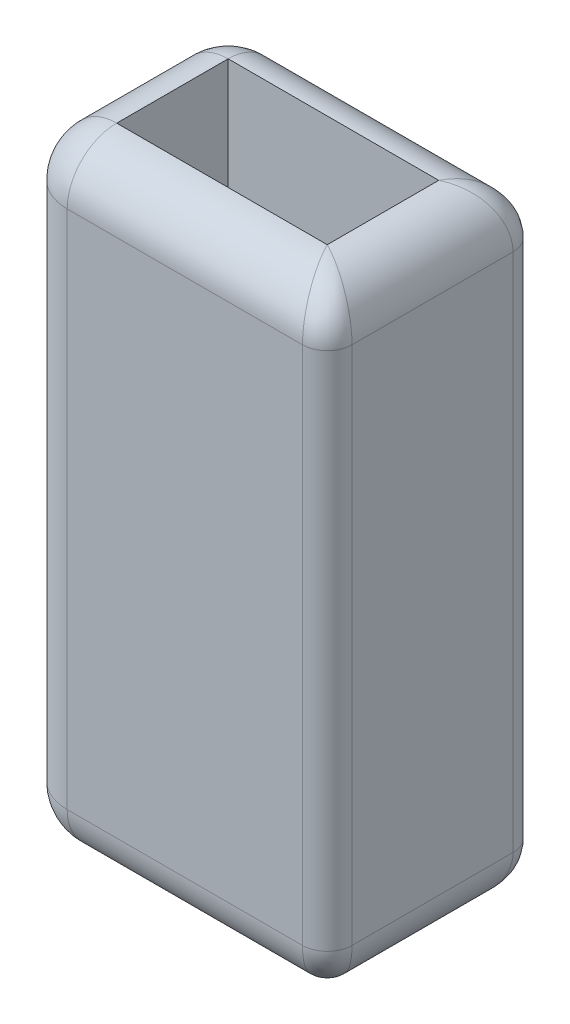
SolidWorks part; units mm, degrees
ref_plane "Front Plane" through (0, 0, 0) normal (0, 0, 1) x (1, 0, 0)
ref_plane "Top Plane" through (0, 0, 0) normal (0, 1, 0) x (1, 0, 0)
ref_plane "Right Plane" through (0, 0, 0) normal (1, 0, 0) x (0, 0, -1)
sketch "Sketch1" plane through (0, 0, 0) normal (0, 1, 0) x (1, 0, 0)
  line L1 (-4.25, 2.25) -> (4.25, 2.25)
  line L2 (-4.25, 2.25) -> (-4.25, -2.25)
  line L3 (-4.25, -2.25) -> (4.25, -2.25)
  line L4 (4.25, 2.25) -> (4.25, -2.25)
  line L5 (-4.25, 4.25) -> (5.25, 4.25)
  line L6 (-6.25, 2.25) -> (-6.25, -2.25)
  line L7 (-4.25, -4.25) -> (5.25, -4.25)
  line L8 (6.25, 3.25) -> (6.25, -3.25)
  arc A0 (5.25, -4.25) -> (6.25, -3.25) centre (5.25, -3.25) ccw
  arc A1 (5.25, 4.25) -> (6.25, 3.25) centre (5.25, 3.25) cw
  arc A2 (-6.25, -2.25) -> (-4.25, -4.25) centre (-4.25, -2.25) ccw
  arc A3 (-4.25, 4.25) -> (-6.25, 2.25) centre (-4.25, 2.25) ccw
  point P4 (0, 2.25)
  point P6 (4.25, 0)
  dimension "D9" = 1
  dimension "D10" = 2
  dimension "D1" = 8.5
  dimension "D2" = 4.5
  dimension "D3" = 0
  dimension "D4" = 0
  dimension "D5" = 2
  dimension "D6" = 2
  dimension "D7" = 2
  dimension "D8" = 2
extrude "Boss-Extrude1" add sketch "Sketch1" along normal blind 25
fillet "Fillet3" radius 2 8 edges at (-5.6642, 25, -3.6642) (-6.25, 25, 0) (-5.6642, 25, 3.6642) (0.5, 25, 4.25) (5.9571, 25, 3.9571) (6.25, 25, 0) (5.9571, 25, -3.9571) (0.5, 25, -4.25)
fillet "Fillet4" radius 2 8 edges at (-5.6642, 0, -3.6642) (-6.25, 0, 0) (-5.6642, 0, 3.6642) (0.5, 0, 4.25) (5.9571, 0, 3.9571) (6.25, 0, 0) (5.9571, 0, -3.9571) (0.5, 0, -4.25)
